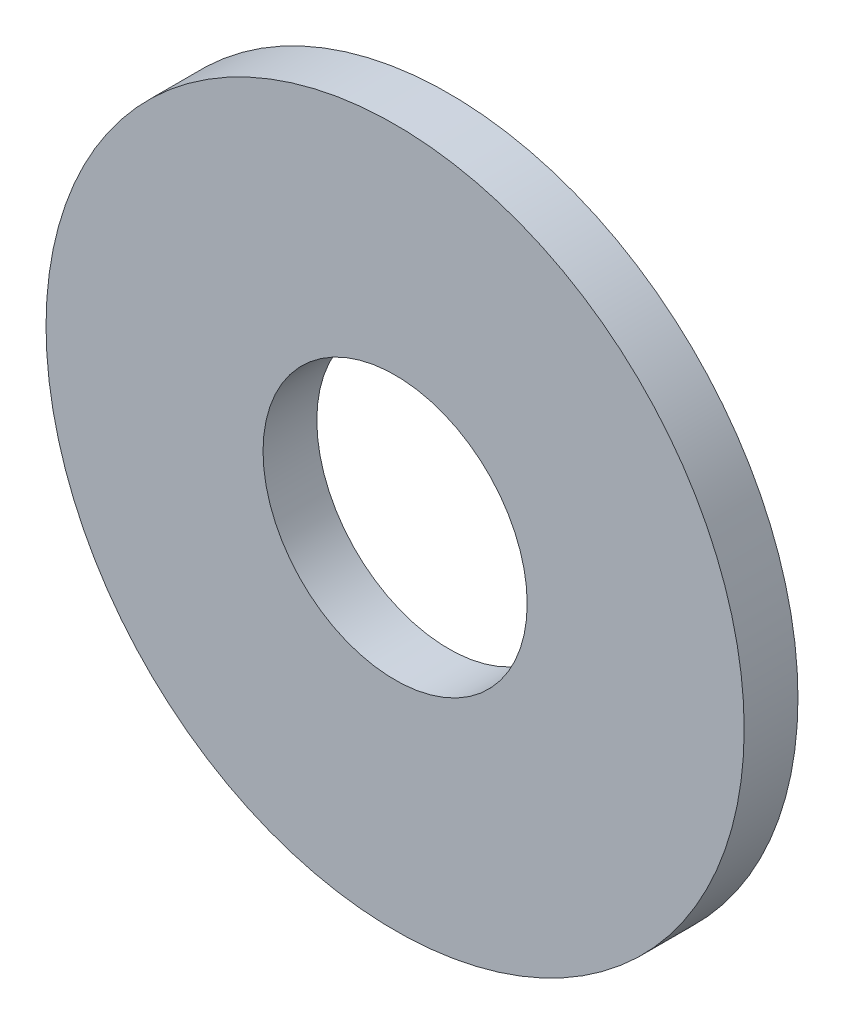
SolidWorks part; units mm, degrees
material "ABS PC"
ref_plane "Front Plane" through (0, 0, 0) normal (0, 0, 1) x (1, 0, 0)
ref_plane "Top Plane" through (0, 0, 0) normal (0, 1, 0) x (1, 0, 0)
ref_plane "Right Plane" through (0, 0, 0) normal (1, 0, 0) x (0, 0, -1)
sketch "Sketch1" plane through (0, 0, 0) normal (0, 0, 1) x (1, 0, 0)
  circle A0 centre (0, 0) radius 3.556
  circle A1 centre (0, 0) radius 9.398
  dimension "ID" = 7.112
  dimension "OD" = 18.796
extrude "Extrude1" add sketch "Sketch1" against normal blind 1.4478
